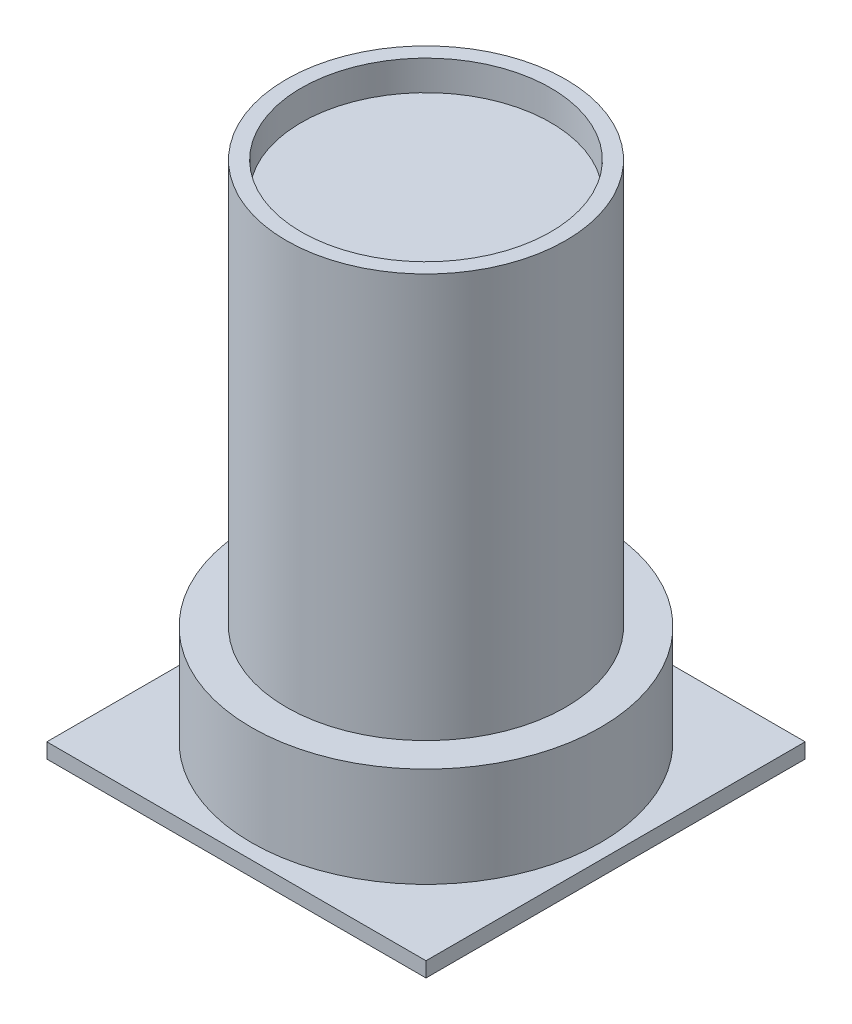
SolidWorks part; units mm, degrees
ref_plane "Front Plane" through (0, 0, 0) normal (0, 0, 1) x (1, 0, 0)
ref_plane "Top Plane" through (0, 0, 0) normal (0, 1, 0) x (1, 0, 0)
ref_plane "Right Plane" through (0, 0, 0) normal (1, 0, 0) x (0, 0, -1)
sketch "Sketch1" plane through (0, 0, 0) normal (0, 1, 0) x (1, 0, 0)
  line L1 (-24.359, 26.1859) -> (13.641, 26.1859)
  line L2 (-24.359, 26.1859) -> (-24.359, -11.8141)
  line L3 (-24.359, -11.8141) -> (13.641, -11.8141)
  line L4 (13.641, 26.1859) -> (13.641, -11.8141)
  dimension "D1" = 38
  dimension "D2" = 38
extrude "Boss-Extrude1" add sketch "Sketch1" along normal blind 1.5
sketch "Sketch2" plane through (0, 1.5, 0) normal (0, 1, 0) x (1, 0, 0)
  circle A0 centre (-5.359, 7.1859) radius 17.5
extrude "Boss-Extrude2" add sketch "Sketch2" along normal blind 10
sketch "Sketch3" plane through (0, 11.5, 0) normal (0, 1, 0) x (1, 0, 0)
  circle A0 centre (-5.359, 7.1859) radius 14
extrude "Boss-Extrude3" add sketch "Sketch3" along normal blind 40.5
sketch "Sketch4" plane through (0, 52, 0) normal (0, 1, 0) x (1, 0, 0)
  circle A0 centre (-5.359, 7.1859) radius 12.5
extrude "Cut-Extrude1" cut sketch "Sketch4" against normal blind 3
